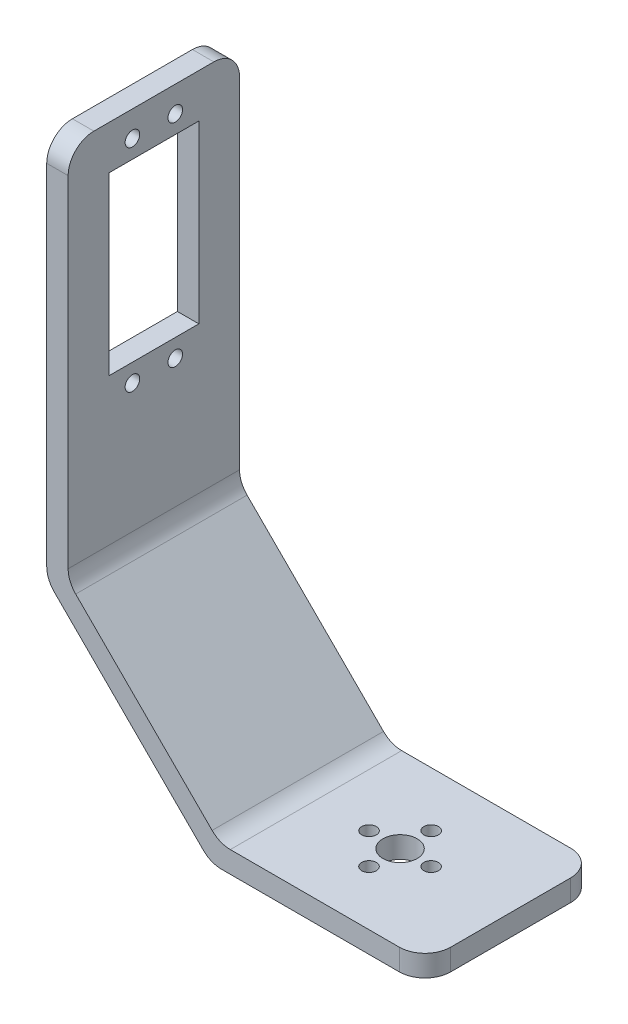
SolidWorks part; units mm, degrees
ref_plane "前视基准面" through (0, 0, 0) normal (0, 0, 1) x (1, 0, 0)
ref_plane "上视基准面" through (0, 0, 0) normal (0, 1, 0) x (1, 0, 0)
ref_plane "右视基准面" through (0, 0, 0) normal (1, 0, 0) x (0, 0, -1)
sketch "草图1" plane through (0, 0, 0) normal (0, 0, 1) x (1, 0, 0)
  line L0 (15.873, -72.2743) -> (-32.056, -72.2743)
  line L3 (-72.4113, -38.9901) -> (-34.127, -77.2743)
  line L4 (-34.127, -77.2743) -> (15.873, -77.2743)
  line L5 (15.873, -77.2743) -> (15.873, -72.2743)
  line L7 (-67.4113, -36.919) -> (-32.056, -72.2743)
  line L8 (-67.4113, -36.919) -> (-67.4113, 51.0099)
  line L9 (-67.4113, 51.0099) -> (-72.4113, 51.0099)
  line L10 (-72.4113, 51.0099) -> (-72.4113, -38.9901)
  dimension "D1" = 135
  dimension "D2" = 50
  dimension "D3" = 5
  dimension "D4" = 5
  dimension "D5" = 5
  dimension "D6" = 90
extrude "凸台-拉伸1" add sketch "草图1" along normal blind 40
sketch "草图2" plane through (0, -72.2743, 0) normal (0, 1, 0) x (1, 0, 0)
  line L0 (15.873, -40) -> (2.6318, -40)
  line L1 (15.873, -40) -> (-32.056, -40) construction
  line L2 (2.6318, -40) -> (15.873, -34)
  line L3 (15.873, -40) -> (15.873, 0) construction
  line L4 (15.873, -34) -> (15.873, -40)
  line L5 (15.873, -20) -> (2.9415, -20) construction
  line L6 (15.873, 0) -> (2.6318, 0)
  line L7 (15.873, -6) -> (15.873, 0)
  line L8 (2.6318, 0) -> (15.873, -6)
fillet "圆角7" radius 6 1 edges at (-34.127, -77.2743, 20) type face fillet first side face at (-53.2692, -58.1322, 20) second side face at (-9.127, -77.2743, 20)
sketch "草图6" plane through (0, -72.2743, 0) normal (0, 1, 0) x (1, 0, 0)
  line L0 (15.873, -20) -> (-19.0843, -20) construction
  line L1 (15.873, -40) -> (15.873, 0) construction
  line L2 (-9.9461, -20) -> (-9.9461, -4.7493) construction
  circle A0 centre (-9.9461, -20) radius 4
  circle A1 centre (-9.9461, -12.75) radius 1.7
  circle A3 centre (-2.6961, -20) radius 1.7
  circle A4 centre (-9.9461, -27.25) radius 1.7
  circle A5 centre (-17.1961, -20) radius 1.7
  point P18 (-9.9461, -20)
  dimension "D1" = 4
extrude "切除-拉伸4" cut sketch "草图6" against normal blind 40
sketch "草图7" plane through (-67.4113, -6.3608, 0) normal (-1, 0, 0) x (0, 0, -1)
  line L0 (-20, 4.9411) -> (-20, -75.7034) construction
  line L2 (-30.5, -6.171) -> (-30.5, -47.171)
  line L3 (-30.5, -47.171) -> (-9.5, -47.171)
  line L4 (-30.5, -6.171) -> (-9.5, -6.171)
  line L5 (-9.5, -6.171) -> (-9.5, -47.171)
  line L6 (-30.5, -26.671) -> (7.4638, -26.671) construction
  circle A0 centre (-25, -1.961) radius 1.7
  circle A1 centre (-15, -1.961) radius 1.7
  circle A2 centre (-25, -51.381) radius 1.7
  circle A3 centre (-15, -51.381) radius 1.7
  point P13 (-20, -6.171)
  point P14 (-20, -47.171)
  dimension "D1" = 49.42
extrude "切除-拉伸5" cut sketch "草图7" along normal blind 10
fillet "圆角8" radius 6 1 edges at (-32.056, -72.2743, 20) type face fillet first side face at (-11.6461, -72.2743, 12.75) second side face at (-49.7336, -54.5967, 20)
fillet "圆角9" radius 6 1 edges at (-72.4113, -38.9901, 20) type face fillet first side face at (-54.1478, -57.2535, 20) second side face at (-72.4113, 6.0099, 20)
fillet "圆角10" radius 6 1 edges at (-67.4113, -36.919, 20) type face fillet first side face at (-67.4113, 7.0455, 20) second side face at (-50.6123, -53.718, 20)
fillet "圆角11" radius 6 1 edges at (-69.9113, 51.0099, 0) type face fillet first side face at (-43.0259, -41.2223, 0) second side face at (-69.9113, 51.0099, 20)
fillet "圆角12" radius 6 1 edges at (-69.9113, 51.0099, 40) type face fillet first side face at (-69.9113, 51.0099, 23) second side face at (-43.0259, -41.2223, 40)
fillet "圆角13" radius 6 1 edges at (15.873, -74.7743, 0) type face fillet first side face at (15.873, -74.7743, 20) second side face at (-43.0259, -42.2223, 0)
fillet "圆角14" radius 6 1 edges at (15.873, -74.7743, 40) type face fillet first side face at (15.873, -74.7743, 23) second side face at (-43.0259, -42.2223, 40)
ref_plane "基准面1" through (0, 0, 20) normal (0, 0, 1) x (1, 0, 0)
sketch "草图8" plane through (0, 0, 20) normal (0, 0, 1) x (1, 0, 0)
  line L0 (-70.6539, -40.7474) -> (-35.8844, -75.517) construction
  line L2 (-56.2177, -55.1837) -> (-49.8537, -61.5477)
  line L3 (-49.8537, -61.5477) -> (-54.0963, -65.7903)
  line L4 (-54.0963, -65.7903) -> (-60.4603, -59.4263)
  line L5 (-60.4603, -59.4263) -> (-56.2177, -55.1837)
  dimension "D1" = 6
  dimension "D2" = 9
extrude "凸台-拉伸2" add sketch "草图8" along normal mid plane 20
sketch "草图9" plane through (-0.517, 0.517, 0) normal (-0.7071, 0.7071, 0) x (0, 0, 1)
  line L1 (30, -78.7727) -> (10, -78.7727) construction
  line L2 (27, -78.7727) -> (13, -78.7727)
  line L3 (13, -78.7727) -> (13, -82.7727)
  line L4 (13, -82.7727) -> (27, -82.7727)
  line L5 (30, -84.7727) -> (10, -84.7727) construction
  line L6 (10, -78.7727) -> (10, -84.7727) construction
  line L7 (27, -78.7727) -> (27, -82.7727)
  point P12 (20, -82.7727)
  dimension "D1" = 2
  dimension "D2" = 3
extrude "切除-拉伸6" cut sketch "草图9" against normal blind 20
fillet "圆角15" radius 2 1 edges at (-57.2783, -62.6083, 10) type face fillet first side face at (-57.2783, -62.6083, 20) second side face at (-55.157, -60.487, 10)
fillet "圆角16" radius 2 1 edges at (-57.2783, -62.6083, 30) type face fillet first side face at (-57.2783, -62.6083, 21) second side face at (-55.157, -60.487, 30)
fillet "圆角17" radius 2 1 edges at (-55.8641, -61.1941, 13) type face fillet first side face at (-54.4499, -59.7799, 13) second side face at (-55.8641, -61.1941, 20)
fillet "圆角18" radius 2 1 edges at (-55.8641, -61.1941, 27) type face fillet first side face at (-54.4499, -59.7799, 27) second side face at (-55.8641, -61.1941, 21)
